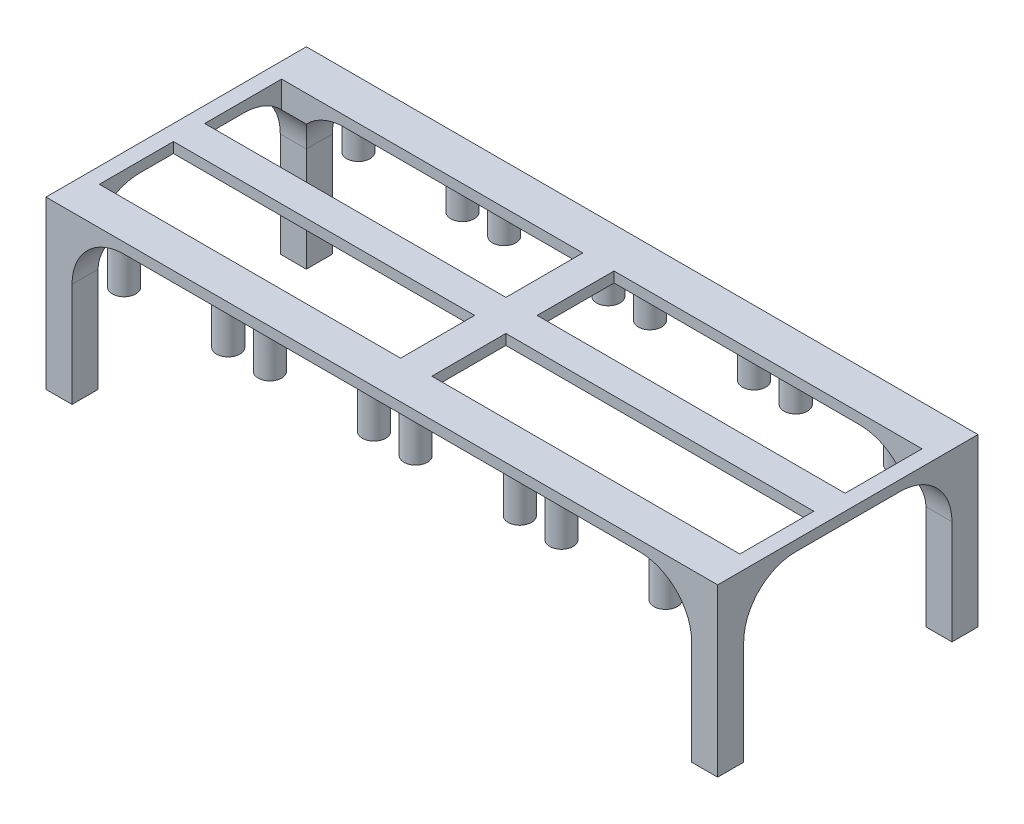
SolidWorks part; units mm, degrees
ref_plane "前视基准面" through (0, 0, 0) normal (0, 0, 1) x (1, 0, 0)
ref_plane "上视基准面" through (0, 0, 0) normal (0, 1, 0) x (1, 0, 0)
ref_plane "右视基准面" through (0, 0, 0) normal (1, 0, 0) x (0, 0, -1)
other "Configuration Table"
sketch "草图1" plane through (0, 0, 0) normal (0, 1, 0) x (1, 0, 0)
  line L1 (-14.9137, 39.4207) -> (10.0863, 39.4207)
  line L2 (-14.9137, 39.4207) -> (-14.9137, -10.5793)
  line L3 (-14.9137, -10.5793) -> (10.0863, -10.5793)
  line L4 (10.0863, 39.4207) -> (10.0863, -10.5793)
  line L5 (-14.9137, 39.4207) -> (10.0863, -10.5793) construction
  line L6 (-14.9137, -10.5793) -> (10.0863, 39.4207) construction
  line L7 (-12.4137, 36.9207) -> (7.5863, 36.9207)
  line L8 (-12.4137, 36.9207) -> (-12.4137, -8.0793)
  line L9 (-12.4137, -8.0793) -> (7.5863, -8.0793)
  line L10 (7.5863, 36.9207) -> (7.5863, -8.0793)
  line L11 (-12.4137, 36.9207) -> (7.5863, -8.0793) construction
  line L12 (-12.4137, -8.0793) -> (7.5863, 36.9207) construction
  circle A0 centre (-12.4137, 36.9207) radius 2.25
  circle A1 centre (7.5863, 36.9207) radius 2.25
  circle A2 centre (7.5863, -8.0793) radius 2.25
  circle A3 centre (-12.4137, -8.0793) radius 2.25
  circle A4 centre (-12.4137, 36.9207) radius 1.5
  circle A5 centre (7.5863, 36.9207) radius 1.5
  circle A6 centre (-12.4137, -8.0793) radius 1.5
  circle A7 centre (7.5863, -8.0793) radius 1.5
  point P0 (-2.4137, 14.4207)
  point P5 (-2.4137, 14.4207)
  dimension "D1" = 50
  dimension "D2" = 25
  dimension "D3" = 45
  dimension "D4" = 20
  dimension "D5" = 2.5
  dimension "D6" = 2.5
extrude "凸台-拉伸1" add sketch "草图1" along normal blind 2 contours A3 L9 A2 L10 A1 L7 A0 L8 | L4 L1 L2 L3 A3 L8 A0 L7 A1 L10 A2 L9 | A5 L10 A1 L7 | L10 A5 L7 | L7 A5 L10 | A5 L7 A1 L10 | A4 L7 A0 L8 | L7 A4 L8 | L8 A4 L7 | A4 L8 A0 L7 | A7 L9 A2 L10 | L9 A7 L10 | A7 L10 A2 L9 | L10 A7 L9 | L9 A6 L8 | A6 L8 A3 L9 | L8 A6 L9 | A6 L9 A3 L8 region at (-2.4137, 0, -38.8617) region at (-12.626, 0, -37.133) region at (-11.7771, 0, -36.2841) region at (-13.5194, 0, -38.0264) region at (-11.2042, 0, -35.7112) region at (-2.4137, 0, -14.4207) region at (7.5863, 0, -39.1071) region at (6.3767, 0, -35.7112) region at (-11.2042, 0, 6.8697) region at (-12.4774, 0, 6.2043) region at (7.7985, 0, -37.133) region at (6.9496, 0, -36.2841) region at (-11.7771, 0, 7.4426) region at (-12.626, 0, 8.2915) region at (9.1322, 0, 6.5333) region at (6.3767, 0, 6.8697) region at (7.7985, 0, 8.2915) region at (6.9496, 0, 7.4426)
sketch "草图2" plane through (0, 0, 0) normal (0, -1, 0) x (1, 0, 0)
  line L0 (-14.9137, -39.4207) -> (-14.9137, 10.5793) construction
  line L1 (-12.4137, 8.0793) -> (7.5863, 8.0793)
  line L2 (-12.4137, 8.0793) -> (-12.4137, -36.9207)
  line L3 (-12.4137, -36.9207) -> (7.5863, -36.9207)
  line L4 (7.5863, 8.0793) -> (7.5863, -36.9207)
  line L5 (-14.9137, -39.4207) -> (10.0863, -39.4207) construction
  circle A0 centre (-12.4137, 8.0793) radius 2.25
  circle A1 centre (7.5863, 8.0793) radius 2.25
  circle A2 centre (-12.4137, -36.9207) radius 2.25
  circle A3 centre (7.5863, -36.9207) radius 2.25
  circle A4 centre (-12.4137, 8.0793) radius 1.5
  circle A5 centre (7.5863, 8.0793) radius 1.5
  circle A6 centre (7.5863, -36.9207) radius 1.5
  circle A7 centre (-12.4137, -36.9207) radius 1.5
  dimension "D1" = 45
  dimension "D2" = 20
  dimension "D3" = 2.5
  dimension "D4" = 2.5
extrude "凸台-拉伸2" add sketch "草图2" along normal blind 8 contours A4 L1 A0 L2 | A4 L2 A0 L1 | A5 L4 A1 L1 | A5 L1 A1 L4 | A7 L2 A2 L3 | A7 L3 A2 L2 | A6 L4 A3 L3 | A6 L3 A3 L4 region at (-13.5194, 0, 9.1849) region at (-11.2042, 0, 6.8697) region at (7.5863, 0, 10.2656) region at (6.3767, 0, 6.8697) region at (-11.2042, 0, -35.7112) region at (-12.4774, 0, -35.0457) region at (9.1322, 0, -35.3748) region at (6.3767, 0, -35.7112)
sketch "草图4" plane through (0, 0, 0) normal (0, -1, 0) x (1, 0, 0)
  line L1 (10.0863, 10.5793) -> (38.0863, 10.5793)
  line L2 (10.0863, 10.5793) -> (10.0863, -39.4207)
  line L3 (10.0863, -39.4207) -> (38.0863, -39.4207)
  line L4 (38.0863, 10.5793) -> (38.0863, -39.4207)
  dimension "D1" = 50
  dimension "D2" = 28
extrude "凸台-拉伸3" add sketch "草图4" against normal blind 2
sketch "草图5" plane through (0, 0, 0) normal (0, -1, 0) x (1, 0, 0)
  line L1 (38.0863, 10.5793) -> (13.0863, 10.5793)
  line L2 (38.0863, 10.5793) -> (38.0863, -39.4207)
  line L3 (38.0863, -39.4207) -> (13.0863, -39.4207)
  line L4 (13.0863, 10.5793) -> (13.0863, -39.4207)
  line L5 (-14.9137, -39.4207) -> (38.0863, -39.4207) construction
  line L7 (15.5863, 8.0793) -> (35.5863, 8.0793)
  line L8 (15.5863, 8.0793) -> (15.5863, -36.9207)
  line L9 (15.5863, -36.9207) -> (35.5863, -36.9207)
  line L10 (35.5863, 8.0793) -> (35.5863, -36.9207)
  circle A0 centre (15.5863, -36.9207) radius 2.25
  circle A1 centre (35.5863, -36.9207) radius 1.5
  circle A2 centre (15.5863, 8.0793) radius 2.25
  circle A3 centre (35.5863, 8.0793) radius 2.25
  circle A4 centre (15.5863, 8.0793) radius 1.5
  circle A5 centre (35.5863, 8.0793) radius 1.3
  circle A6 centre (15.5863, -36.9207) radius 1.5
  circle A7 centre (35.5863, -36.9207) radius 2.25
  dimension "D1" = 50
  dimension "D2" = 25
  dimension "D3" = 45
  dimension "D4" = 20
  dimension "D5" = 2.5
  dimension "D6" = 2.5
extrude "凸台-拉伸4" add sketch "草图5" along normal blind 8 contours A4 L7 A2 L8 | A4 L8 A2 L7 | A5 L10 A3 L7 | A5 L7 A3 L10 | A6 L8 A0 L9 | A6 L9 A0 L8 | L9 A7 L10 A1 | L10 A7 L9 A1 region at (14.4806, 0, 9.1849) region at (16.7958, 0, 6.8697) region at (35.5863, 0, 10.2656) region at (34.4293, 0, 6.9223) region at (16.7958, 0, -35.7112) region at (15.5226, 0, -35.0457) region at (37.1322, 0, -35.3748) region at (34.3767, 0, -35.7112)
sketch "草图6" plane through (0, 0, 0) normal (0, -1, 0) x (1, 0, 0)
  line L1 (38.0863, 10.5793) -> (66.0863, 10.5793)
  line L2 (38.0863, 10.5793) -> (38.0863, -39.4207)
  line L3 (38.0863, -39.4207) -> (66.0863, -39.4207)
  line L4 (66.0863, 10.5793) -> (66.0863, -39.4207)
  dimension "D1" = 50
  dimension "D2" = 28
extrude "凸台-拉伸5" add sketch "草图6" against normal blind 2
sketch "草图7" plane through (0, 0, 0) normal (0, -1, 0) x (1, 0, 0)
  line L1 (66.0863, 10.5793) -> (41.0863, 10.5793)
  line L2 (66.0863, 10.5793) -> (66.0863, -39.4207)
  line L3 (66.0863, -39.4207) -> (41.0863, -39.4207)
  line L4 (41.0863, 10.5793) -> (41.0863, -39.4207)
  line L5 (-14.9137, -39.4207) -> (66.0863, -39.4207) construction
  line L7 (43.5863, 8.0793) -> (63.5863, 8.0793)
  line L8 (43.5863, 8.0793) -> (43.5863, -36.9207)
  line L9 (43.5863, -36.9207) -> (63.5863, -36.9207)
  line L10 (63.5863, 8.0793) -> (63.5863, -36.9207)
  circle A0 centre (43.5863, 8.0793) radius 2.25
  circle A1 centre (43.5863, 8.0793) radius 1.5
  circle A2 centre (63.5863, 8.0793) radius 2.25
  circle A3 centre (63.5863, 8.0793) radius 1.5
  circle A4 centre (43.5863, -36.9207) radius 2.25
  circle A5 centre (43.5863, -36.9207) radius 1.5
  circle A7 centre (63.5863, -36.9207) radius 2.25
  circle A8 centre (63.5863, -36.9207) radius 1.5
  dimension "D1" = 50
  dimension "D2" = 25
  dimension "D3" = 45
  dimension "D4" = 20
  dimension "D5" = 2.5
  dimension "D6" = 2.5
extrude "凸台-拉伸6" add sketch "草图7" along normal blind 8 contours A1 L7 A0 L8 | A1 L8 A0 L7 | A3 L10 A2 L7 | A3 L7 A2 L10 | A5 L8 A4 L9 | A5 L9 A4 L8 | A8 L9 A7 L10 | A8 L10 A7 L9 region at (42.4806, 0, 9.1849) region at (44.7958, 0, 6.8697) region at (63.5863, 0, 10.2656) region at (62.3767, 0, 6.8697) region at (44.7958, 0, -35.7112) region at (43.5226, 0, -35.0457) region at (65.1322, 0, -35.3748) region at (62.3767, 0, -35.7112)
sketch "草图8" plane through (0, 0, 0) normal (0, -1, 0) x (1, 0, 0)
  line L1 (66.0863, 10.5793) -> (94.0863, 10.5793)
  line L2 (66.0863, 10.5793) -> (66.0863, -39.4207)
  line L3 (66.0863, -39.4207) -> (94.0863, -39.4207)
  line L4 (94.0863, 10.5793) -> (94.0863, -39.4207)
  dimension "D1" = 50
  dimension "D2" = 28
extrude "凸台-拉伸7" add sketch "草图8" against normal blind 2
sketch "草图9" plane through (0, 0, 0) normal (0, -1, 0) x (1, 0, 0)
  line L1 (94.0863, 10.5793) -> (69.0863, 10.5793)
  line L2 (94.0863, 10.5793) -> (94.0863, -39.4207)
  line L3 (94.0863, -39.4207) -> (69.0863, -39.4207)
  line L4 (69.0863, 10.5793) -> (69.0863, -39.4207)
  line L5 (-14.9137, -39.4207) -> (94.0863, -39.4207) construction
  line L7 (71.5863, 8.0793) -> (91.5863, 8.0793)
  line L8 (71.5863, 8.0793) -> (71.5863, -36.9207)
  line L9 (71.5863, -36.9207) -> (91.5863, -36.9207)
  line L10 (91.5863, 8.0793) -> (91.5863, -36.9207)
  circle A0 centre (71.5863, 8.0793) radius 2.25
  circle A1 centre (71.5863, 8.0793) radius 1.5
  circle A2 centre (91.5863, 8.0793) radius 2.25
  circle A3 centre (91.5863, 8.0793) radius 1.5
  circle A4 centre (71.5863, -36.9207) radius 2.25
  circle A5 centre (71.5863, -36.9207) radius 1.5
  circle A6 centre (91.5863, -36.9207) radius 2.25
  circle A7 centre (91.5863, -36.9207) radius 1.5
  dimension "D1" = 50
  dimension "D2" = 25
  dimension "D3" = 45
  dimension "D4" = 20
  dimension "D5" = 2.5
  dimension "D6" = 2.5
extrude "凸台-拉伸8" add sketch "草图9" along normal blind 8 contours A1 L7 A0 L8 | A1 L8 A0 L7 | A3 L10 A2 L7 | A3 L7 A2 L10 | A5 L8 A4 L9 | A5 L9 A4 L8 | A7 L10 A6 L9 | A7 L9 A6 L10 region at (70.4806, 0, 9.1849) region at (72.7958, 0, 6.8697) region at (91.5863, 0, 10.2656) region at (90.3767, 0, 6.8697) region at (72.7958, 0, -35.7112) region at (71.5226, 0, -35.0457) region at (93.1322, 0, -35.3748) region at (90.3767, 0, -35.7112)
ref_plane "基准面1" through (39.5863, 0, 0) normal (-1, 0, 0) x (0, 0, 1)
sketch "草图10" plane through (-14.9137, 0, 0) normal (-1, 0, 0) x (0, 0, 1)
  line L1 (-39.4207, 2) -> (10.5793, 2)
  line L2 (-39.4207, 2) -> (-39.4207, 0)
  line L3 (-39.4207, 0) -> (10.5793, 0)
  line L4 (10.5793, 2) -> (10.5793, 0)
  dimension "D1" = 2
  dimension "D2" = 50
extrude "凸台-拉伸9" add sketch "草图10" along normal blind 10
sketch "草图11" plane through (0, 0, 0) normal (0, -1, 0) x (1, 0, 0)
  line L7 (-24.9137, 10.5793) -> (-19.9137, 10.5793)
  line L8 (-24.9137, 10.5793) -> (-24.9137, 5.5793)
  line L9 (-24.9137, 5.5793) -> (-19.9137, 5.5793)
  line L10 (-19.9137, 10.5793) -> (-19.9137, 5.5793)
  line L11 (-24.9137, -39.4207) -> (-19.9137, -39.4207)
  line L12 (-24.9137, -39.4207) -> (-24.9137, -34.4207)
  line L13 (-24.9137, -34.4207) -> (-19.9137, -34.4207)
  line L14 (-19.9137, -39.4207) -> (-19.9137, -34.4207)
  dimension "D1" = 5
  dimension "D2" = 5
extrude "凸台-拉伸10" add sketch "草图11" along normal blind 30
mirror "镜向1" about plane through (39.5863, 0, 0) normal (-1, 0, 0) of "凸台-拉伸9", "凸台-拉伸10"
sketch "草图12" plane through (0, 0, 0) normal (0, -1, 0) x (1, 0, 0)
  line L1 (-24.9137, 5.824) -> (104.0863, 5.824)
  line L2 (-24.9137, 5.824) -> (-24.9137, -34.176)
  line L3 (-24.9137, -34.176) -> (104.0863, -34.176)
  line L4 (104.0863, 5.824) -> (104.0863, -34.176)
  line L6 (-24.9137, -34.4207) -> (-24.9137, 5.5793) construction
  line L7 (104.0863, -34.4207) -> (104.0863, 5.5793) construction
  line L9 (-21.9137, 3.324) -> (101.0863, 3.324)
  line L10 (-21.9137, 3.324) -> (-21.9137, -31.676)
  line L11 (-21.9137, -31.676) -> (101.0863, -31.676)
  line L12 (101.0863, 3.324) -> (101.0863, -31.676)
  line L13 (-21.9137, -10.8982) -> (101.0863, -10.8982)
  line L14 (-21.9137, -10.8982) -> (-21.9137, -16.8982)
  line L15 (-21.9137, -16.8982) -> (101.0863, -16.8982)
  line L16 (101.0863, -10.8982) -> (101.0863, -16.8982)
  line L17 (35.9313, 3.324) -> (41.9313, 3.324)
  line L18 (35.9313, 3.324) -> (35.9313, -31.676)
  line L19 (35.9313, -31.676) -> (41.9313, -31.676)
  line L20 (41.9313, 3.324) -> (41.9313, -31.676)
  dimension "D1" = 40
  dimension "D2" = 129
  dimension "D3" = 35
  dimension "D4" = 123
  dimension "D5" = 2.5
  dimension "D6" = 3
  dimension "D7" = 6
  dimension "D8" = 123
  dimension "D9" = 35
  dimension "D10" = 6
extrude "切除-拉伸2" cut sketch "草图12" against normal blind 2 contours L9 L20 L13 L12 | L15 L20 L11 L12 | L18 L15 L10 L11 | L18 L9 L10 L13 region at (7.0088, 0, -3.7871) region at (71.5088, 0, -3.7871) region at (7.0088, 0, -24.2871) region at (71.5088, 0, -24.2871)
fillet "圆角1" radius 10 8 edges at (99.0863, 0, 8.0793) (101.5863, 0, 5.5793) (101.5863, 0, -34.4207) (99.0863, 0, -36.9207) (-19.9137, 0, 8.0793) (-22.4137, 0, 5.5793) (-19.9137, 0, -36.9207) (-22.4137, 0, -34.4207)
